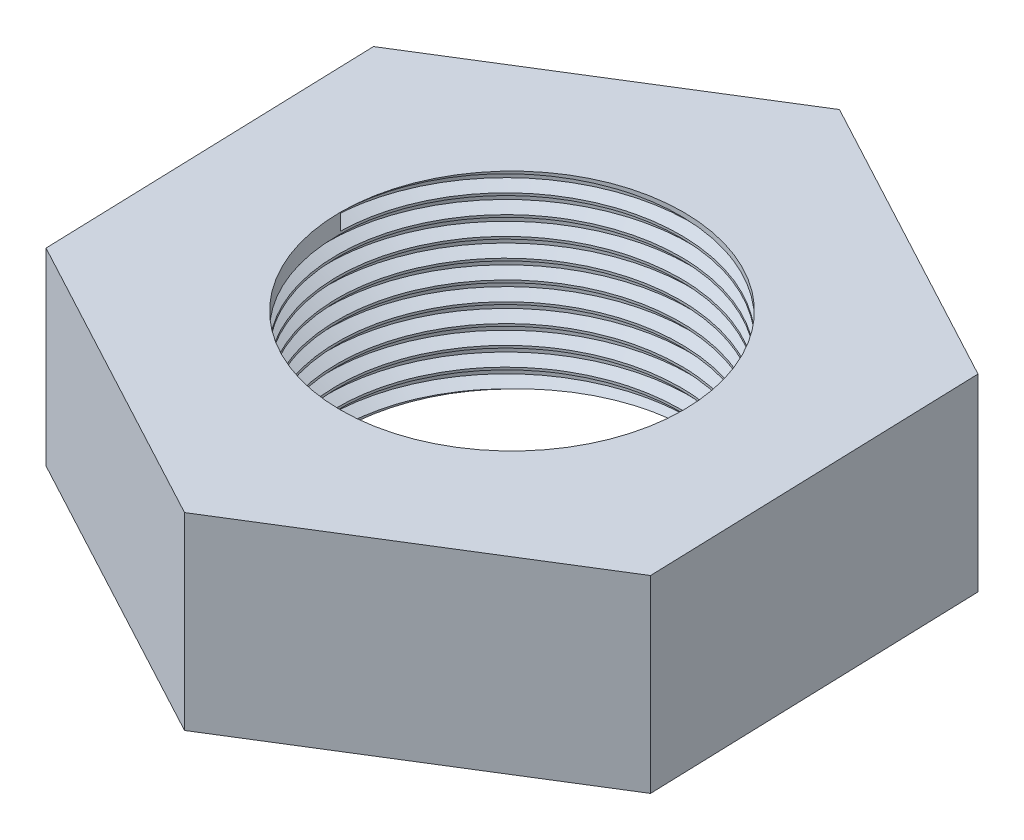
SolidWorks part; units mm, degrees
ref_plane "Front Plane" through (0, 0, 0) normal (0, 0, 1) x (1, 0, 0)
ref_plane "Top Plane" through (0, 0, 0) normal (0, 1, 0) x (1, 0, 0)
ref_plane "Right Plane" through (0, 0, 0) normal (1, 0, 0) x (0, 0, -1)
sketch "Sketch1" plane through (0, 0, 0) normal (0, 1, 0) x (1, 0, 0)
  line L1 (47.4239, -25.4) -> (45.709, 28.3703)
  line L2 (45.709, 28.3703) -> (-1.7149, 53.7703)
  line L3 (-1.7149, 53.7703) -> (-47.4239, 25.4)
  line L4 (-47.4239, 25.4) -> (-45.709, -28.3703)
  line L5 (-45.709, -28.3703) -> (1.7149, -53.7703)
  line L6 (1.7149, -53.7703) -> (47.4239, -25.4)
  circle A0 centre (0, 0) radius 46.5901 construction
extrude "Boss-Extrude1" add sketch "Sketch1" along normal blind 30
sketch "Sketch2" plane through (0, 30, 0) normal (0, 1, 0) x (1, 0, 0)
  circle A0 centre (0, 0) radius 27.2543
extrude "Cut-Extrude1" cut sketch "Sketch2" against normal blind 30 contours A0
thread "Thread1" pitch 3 start angle 0, offset 0, length 30, pitch 3, diameter 54.5086
ref_plane "Plane1" through (-27.2543, 27, 0) normal (0, 0, -1) x (1, 0, 0)
sketch "Thread Profile1" plane through (-27.2543, 27, 0) normal (0, 0, -1) x (1, 0, 0)
  line L0 (0, 0) -> (0, 3) construction
  line L11 (0, 0) -> (0, 2.625)
  line L12 (0, 2.625) -> (-1.6238, 1.6875)
  line L13 (-1.6238, 1.6875) -> (-1.6238, 0.9375)
  line L15 (-1.6238, 0.9375) -> (0, 0)
  line L17 (-1.6238, 1.3125) -> (0, 1.3125) construction
  point P2 (0, 0)
  dimension "Pitch" = 3
  dimension "Profile_Angle" = 60
  dimension "Profile_Land" = 0.75
  dimension "Profile_Height" = 1.6238
